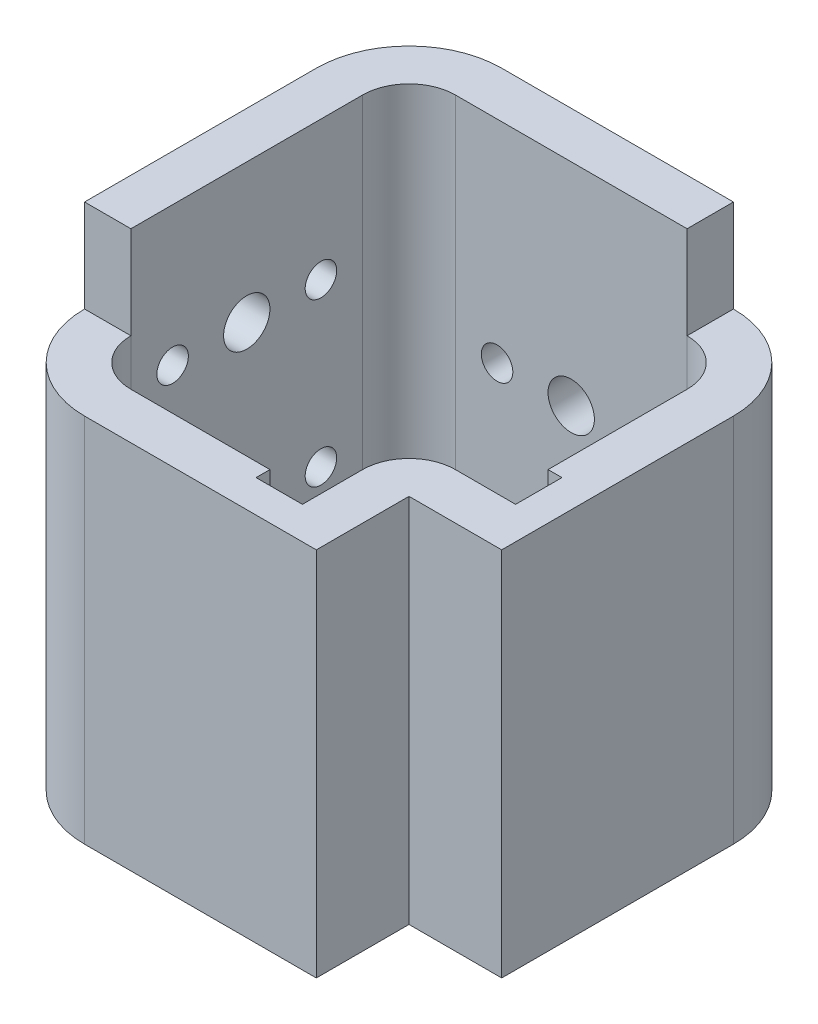
SolidWorks part; units mm, degrees
note: The reader was unsure of these and kept them because the rebuilt part matched: shared geometry of "Sketch1<5>".
material "ABS"
ref_plane "Front Plane" through (0, 0, 0) normal (0, 0, 1) x (1, 0, 0)
ref_plane "Top Plane" through (0, 0, 0) normal (0, 1, 0) x (1, 0, 0)
ref_plane "Right Plane" through (0, 0, 0) normal (1, 0, 0) x (0, 0, -1)
sketch "Sketch1" plane through (0, 0, 0) normal (0, 1, 0) x (1, 0, 0)
  line L0 (25, 45) -> (-25, 45)
  line L5 (25, -35) -> (-25, -35)
  line L6 (35, -25) -> (35, 25)
  line L7 (25, 35) -> (-25, 35)
  line L8 (-35, -25) -> (-35, 25)
  line L9 (35, -35) -> (-35, 35) construction
  line L10 (35, 35) -> (-35, -35) construction
  line L11 (-45, -25) -> (-45, 25)
  line L12 (25, -45) -> (-25, -45)
  line L13 (45, -25) -> (45, 25)
  line L14 (25, 485) -> (-25, 485) construction
  line L29 (35, -25) -> (25, -25)
  line L30 (35, -25) -> (45, -25)
  line L31 (25, -35) -> (25, -45)
  line L32 (25, -45) -> (45, -45)
  line L33 (45, -25) -> (45, -45)
  line L34 (25, -35) -> (5, -35)
  line L35 (25, -35) -> (25, -38)
  line L36 (25, -38) -> (5, -38)
  line L37 (5, -35) -> (5, -38)
  line L38 (35, -25) -> (38, -25)
  line L39 (35, -25) -> (35, -5)
  line L40 (35, -5) -> (38, -5)
  line L41 (38, -25) -> (38, -5)
  line L42 (25, -25) -> (25, -35)
  line L43 (35, -15) -> (25, -15)
  line L44 (15, -25) -> (15, -35)
  line L45 (35, -15) -> (15, -15) construction
  line L46 (15, -15) -> (15, -35) construction
  line L47 (35, -15) -> (38, -15)
  line L48 (15, -35) -> (15, -38)
  line L49 (5, 488) -> (5, 485) construction
  line L50 (25, 488) -> (5, 488) construction
  arc A0 (35, 25) -> (25, 35) centre (25, 25) ccw
  arc A1 (25, -35) -> (35, -25) centre (25, -25) ccw
  arc A2 (-25, -35) -> (-35, -25) centre (-25, -25) cw
  arc A3 (-25, 35) -> (-35, 25) centre (-25, 25) ccw
  arc A4 (-25, 45) -> (-45, 25) centre (-25, 25) ccw
  arc A5 (-25, -45) -> (-45, -25) centre (-25, -25) cw
  arc A6 (25, -45) -> (45, -25) centre (25, -25) ccw
  arc A7 (45, 25) -> (25, 45) centre (25, 25) ccw
  arc A8 (25, -15) -> (15, -25) centre (25, -25) ccw
  point P0 (0, 0)
  dimension "D1" = 10
  dimension "D4" = 10
  dimension "D3" = 10
  dimension "D2" = 10
extrude "Boss-Extrude1" add sketch "Sketch1" along normal up to surface (54.6167 mm away) and the other way up to surface (45.3833 mm away)
sketch "Sketch2" plane through (0, 0, -45) normal (0, 0, -1) x (-1, 0, 0)
  line L0 (-25, 54.6167) -> (-25, -45.3833) construction
  line L1 (-25, 34.6167) -> (-45, 34.6167)
  line L2 (-25, 34.6167) -> (-25, 54.6167)
  line L3 (-25, 54.6167) -> (-45, 54.6167)
  line L4 (-45, 34.6167) -> (-45, 54.6167)
  line L5 (-25, 54.6167) -> (25, 54.6167) construction
  dimension "D1" = 20
extrude "Cut-Extrude1" cut sketch "Sketch2" against normal through all
sketch "Sketch3" plane through (-45, 0, 0) normal (-1, 0, 0) x (0, 0, 1)
  line L0 (25, 54.6167) -> (25, -45.3833) construction
  line L1 (25, 34.6167) -> (45, 34.6167)
  line L2 (25, 34.6167) -> (25, 54.6167)
  line L3 (25, 54.6167) -> (45, 54.6167)
  line L4 (45, 34.6167) -> (45, 54.6167)
  line L5 (25, 54.6167) -> (-25, 54.6167) construction
  dimension "D1" = 20
extrude "Cut-Extrude2" cut sketch "Sketch3" against normal through all
extrude "Boss-Extrude2" add sketch "Sketch1<5>" along normal up to surface and the other way up to surface contours L43 A8 L44 L5 L42 L29 L6 | L47 L6 L30 L41 | L5 L48 L36 L31
sketch "Sketch1<5>" plane through (0, 0, 0) normal (0, 1, 0) x (1, 0, 0) same geometry as "Sketch1"
sketch "Sketch4" plane through (-45, 0, 0) normal (-1, 0, 0) x (0, 0, 1)
  circle A0 centre (0.0016, 24.6167) radius 5 construction
  circle A1 centre (0.0016, -10.3833) radius 5 construction
  circle A2 centre (0.0016, 24.6167) radius 5
  circle A3 centre (0.0016, -10.3833) radius 5
  circle A4 centre (16.0016, -10.3833) radius 3.4 construction
  circle A5 centre (-15.9984, -10.3833) radius 3.4 construction
  circle A6 centre (16.0016, 24.6167) radius 3.4 construction
  circle A7 centre (-15.9984, 24.6167) radius 3.4 construction
  circle A8 centre (16.0016, -10.3833) radius 3.4
  circle A9 centre (-15.9984, -10.3833) radius 3.4
  circle A10 centre (16.0016, 24.6167) radius 3.4
  circle A11 centre (-15.9984, 24.6167) radius 3.4
sketch "Sketch5" plane through (0, 0, -45) normal (0, 0, -1) x (-1, 0, 0)
  circle A0 centre (0, 9.0167) radius 5 construction
  circle A1 centre (0, -25.9833) radius 5 construction
  circle A2 centre (0, 9.0167) radius 5
  circle A3 centre (0, -25.9833) radius 5
  circle A4 centre (16, -25.9833) radius 3.4 construction
  circle A5 centre (-16, -25.9833) radius 3.4 construction
  circle A6 centre (-16, 9.0167) radius 3.4 construction
  circle A7 centre (16, 9.0167) radius 3.4 construction
  circle A8 centre (16, -25.9833) radius 3.4
  circle A9 centre (-16, -25.9833) radius 3.4
  circle A10 centre (-16, 9.0167) radius 3.4
  circle A11 centre (16, 9.0167) radius 3.4
extrude "Cut-Extrude3" cut sketch "Sketch5" against normal up to next
extrude "Cut-Extrude4" cut sketch "Sketch4" against normal up to next
